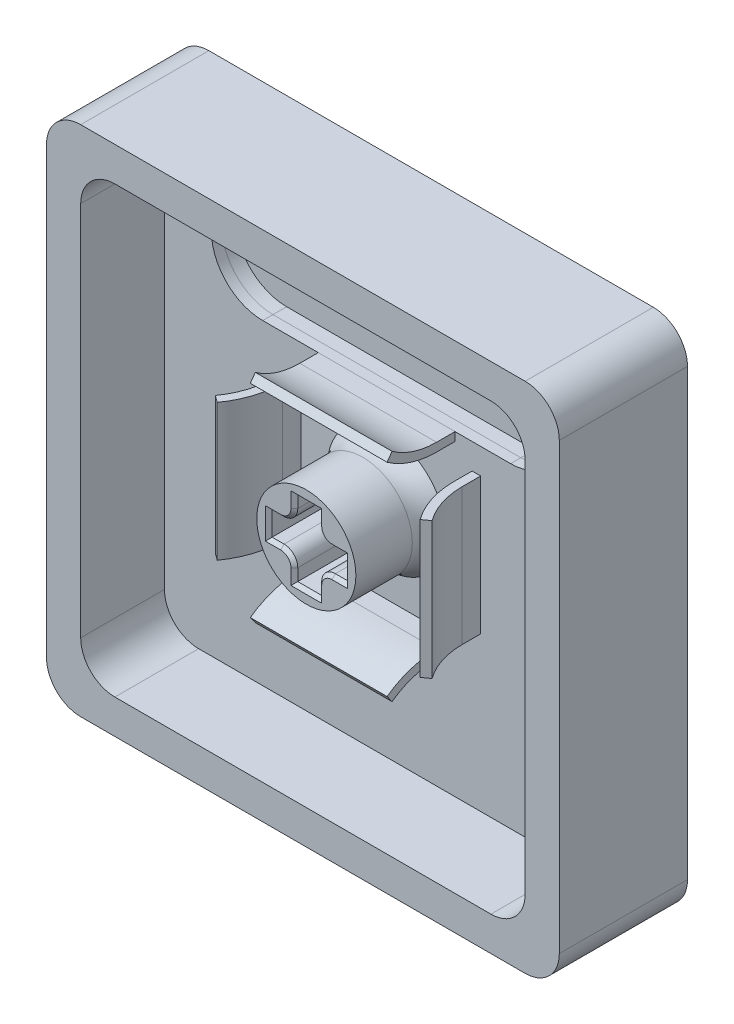
SolidWorks part; units mm, degrees
note: '?' marks a value the reader was unsure of. The reader was unsure of these and kept them because the rebuilt part matched: shared geometry of "草图1<6>", "草图1<7>".
other "标注1"
sketch "草图2" plane through (15, -15, 10) normal (0.3933, -0.7926, 0.466) x (0.9059, 0.4207, -0.0491)
ref_plane "前视基准面" through (0, 0, 0) normal (0, 0, 1) x (1, 0, 0)
ref_plane "上视基准面" through (0, 0, 0) normal (0, 1, 0) x (1, 0, 0)
ref_plane "右视基准面" through (0, 0, 0) normal (1, 0, 0) x (0, 0, -1)
sketch "草图1" plane through (0, 0, 0) normal (0, 0, 1) x (1, 0, 0)
  line L0 (-13, 15) -> (13, 15)
  line L1 (-11, 13) -> (11, 13)
  line L2 (-13, 11) -> (-13, -11)
  line L3 (-11, -13) -> (11, -13)
  line L4 (13, 11) -> (13, -11)
  line L5 (0, -13) -> (0, 13) construction
  line L6 (-13, 0) -> (13, 0) construction
  line L7 (15, 13) -> (15, -13)
  line L8 (-13, -15) -> (13, -15)
  line L9 (-15, 13) -> (-15, -13)
  line L10 (-13, -13) -> (13, -13) construction
  line L11 (-2.2, 0.7) -> (2.2, 0.7)
  line L12 (-2.2, 0.7) -> (-2.2, -0.7)
  line L13 (-2.2, -0.7) -> (2.2, -0.7)
  line L14 (2.2, 0.7) -> (2.2, -0.7)
  line L15 (0, -0.7) -> (0, 0.7) construction
  line L16 (-2.2, 0) -> (2.2, 0) construction
  line L17 (-0.7, 2.2) -> (0.7, 2.2)
  line L18 (-0.7, 2.2) -> (-0.7, -2.2)
  line L19 (-0.7, -2.2) -> (0.7, -2.2)
  line L20 (0.7, 2.2) -> (0.7, -2.2)
  line L21 (0, -2.2) -> (0, 2.2) construction
  line L22 (-0.7, 0) -> (0.7, 0) construction
  line L23 (13, 13) -> (13, -13) construction
  line L24 (-13, 13) -> (13, 13) construction
  line L25 (-13, 13) -> (-13, -13) construction
  line L26 (-15, 15) -> (-15, -15) construction
  line L27 (-15, -15) -> (15, -15) construction
  line L28 (15, 15) -> (15, -15) construction
  line L29 (-15, 15) -> (15, 15) construction
  line L36 (-13, 0) -> (-2.5, 0) construction
  circle A0 centre (0, 0) radius 2.9
  arc A1 (11, -13) -> (13, -11) centre (11, -11) ccw
  arc A2 (13, 11) -> (11, 13) centre (11, 11) ccw
  arc A3 (-13, 11) -> (-11, 13) centre (-11, 11) cw
  arc A4 (-13, -11) -> (-11, -13) centre (-11, -11) ccw
  arc A5 (-15, -13) -> (-13, -15) centre (-13, -13) ccw
  arc A6 (13, -15) -> (15, -13) centre (13, -13) ccw
  arc A7 (15, 13) -> (13, 15) centre (13, 13) ccw
  arc A8 (-15, 13) -> (-13, 15) centre (-13, 13) cw
  point P0 (0, 0)
  point P19 (13, -13)
  point P66 (0.0162, 0.0162)
  dimension "D4" = 5.8
  dimension "D9" = 2
  dimension "D1" = 30
  dimension "D2" = 30
  dimension "D5" = 4.4
  dimension "D6" = 1.4
  dimension "D7" = 4.4
  dimension "D8" = 1.4
  dimension "D3" = 2
extrude "凸台-拉伸1" add sketch "草图1" along normal blind 5.5 contours A8 L9 A5 L8 A6 L7 A7 L0 A4 L2 A3 L1 A2 L4 A1 L3
extrude "凸台-拉伸2" add sketch "草图1<6>" along normal blind 5.3 separate body contours A0 L17 L20 L11 L14 L13 L19 L18 L12
sketch "草图1<6>" plane through (0, 0, 0) normal (0, 0, 1) x (1, 0, 0) same geometry as "草图1"
extrude "凸台-拉伸3" add sketch "草图1<7>" against normal blind 2 contours L8 A6 L7 A7 L0 A8 L9 A5
sketch "草图1<7>" plane through (0, 0, 0) normal (0, 0, 1) x (1, 0, 0) same geometry as "草图1"
sketch "草图3" plane through (0, 0, 0) normal (0, 0, 1) x (1, 0, 0)
  line L8 (0.7, 0.7) -> (0.7, 2.2)
  line L10 (0.7, 0.7) -> (0.7, 2.2)
  line L15 (-0.7, 0.7) -> (-2.2, 0.7)
  line L16 (-2.2, 0.7) -> (-2.2, -0.7)
  line L17 (-2.2, -0.7) -> (-0.7, -0.7)
  line L19 (0.7, 2.2) -> (-0.7, 2.2)
  line L20 (0.7, 2.2) -> (-0.7, 2.2)
  line L21 (0.7, -0.7) -> (2.2, -0.7)
  line L22 (2.2, -0.7) -> (2.2, 0.7)
  line L23 (2.2, 0.7) -> (0.7, 0.7)
  line L27 (-0.7, 0.7) -> (-2.2, 0.7)
  line L28 (-2.2, 0.7) -> (-2.2, -0.7)
  line L29 (-2.2, -0.7) -> (-0.7, -0.7)
  line L33 (0.7, -0.7) -> (2.2, -0.7)
  line L34 (2.2, -0.7) -> (2.2, 0.7)
  line L35 (2.2, 0.7) -> (0.7, 0.7)
  line L36 (-0.7, 2.2) -> (-0.7, 0.7)
  line L37 (-0.7, 2.2) -> (-0.7, 0.7)
  line L38 (-0.7, -0.7) -> (-0.7, -2.2)
  line L39 (-0.7, -0.7) -> (-0.7, -2.2)
  line L40 (-0.7, -2.2) -> (0.7, -2.2)
  line L41 (-0.7, -2.2) -> (0.7, -2.2)
  line L42 (0.7, -2.2) -> (0.7, -0.7)
  line L43 (0.7, -2.2) -> (0.7, -0.7)
  dimension "D1" = 0
extrude "凸台-拉伸4" add sketch "草图3" along normal blind 2
sketch "草图5" plane through (0, 0, 0) normal (0, 0, 1) x (1, 0, 0)
  line L6 (7.25, 8.5) -> (-7.25, 8.5) construction
  line L7 (7.25, 5.5) -> (-7.25, 5.5)
  line L9 (7.25, 11.5) -> (-7.25, 11.5)
  line L10 (0, 0) -> (0, -50000) construction
  arc A0 (7.25, 5.5) -> (7.25, 11.5) centre (7.25, 8.5) ccw
  arc A1 (-7.25, 11.5) -> (-7.25, 5.5) centre (-7.25, 8.5) ccw
  point P2 (0, 8.5)
  dimension "D2" = 3
  dimension "D1" = 14.5
  dimension "D3" = 8.5
extrude "切除-拉伸1" cut sketch "草图5" against normal up to next
sketch "草图6" plane through (0, 0, -2) normal (0, 0, -1) x (-1, 0, 0)
  line L10 (7.25, 5.5) -> (-7.25, 5.5) construction
  line L11 (-7.25, 11.5) -> (7.25, 11.5) construction
  line L12 (7.25, 5.5) -> (-7.25, 5.5)
  line L13 (-7.25, 11.5) -> (7.25, 11.5)
  arc A0 (7.25, 5.5) -> (7.25, 11.5) centre (7.25, 8.5) ccw construction
  arc A1 (-7.25, 11.5) -> (-7.25, 5.5) centre (-7.25, 8.5) ccw construction
  arc A2 (7.25, 5.5) -> (7.25, 11.5) centre (7.25, 8.5) ccw
  arc A3 (-7.25, 11.5) -> (-7.25, 5.5) centre (-7.25, 8.5) ccw
extrude "凸台-拉伸6" add sketch "草图6" against normal blind 1.2 separate body
sketch "草图7" plane through (0, 0, 0) normal (0, 0, 1) x (1, 0, 0)
  line L0 (7.25, 5.5) -> (-7.25, 5.5) construction
  line L1 (7.25, 11.5) -> (-7.25, 11.5) construction
  line L2 (7.25, 5.5) -> (-7.25, 5.5)
  line L3 (7.25, 11.5) -> (-7.25, 11.5)
  line L4 (-13, 11) -> (-13, -11)
  line L5 (-11, -13) -> (11, -13)
  line L6 (13, -11) -> (13, 11)
  line L7 (11, 13) -> (-11, 13)
  line L8 (-13, 11) -> (-13, -11)
  line L9 (-11, -13) -> (11, -13)
  line L10 (13, -11) -> (13, 11)
  line L11 (11, 13) -> (-11, 13)
  circle A0 centre (0, 0) radius 2.9 construction
  circle A1 centre (0, 0) radius 2.9
  arc A2 (7.25, 5.5) -> (7.25, 11.5) centre (7.25, 8.5) ccw construction
  arc A3 (-7.25, 11.5) -> (-7.25, 5.5) centre (-7.25, 8.5) ccw construction
  arc A4 (-13, -11) -> (-11, -13) centre (-11, -11) ccw
  arc A5 (11, -13) -> (13, -11) centre (11, -11) ccw
  arc A6 (13, 11) -> (11, 13) centre (11, 11) ccw
  arc A7 (-11, 13) -> (-13, 11) centre (-11, 11) ccw
  arc A8 (-13, -11) -> (-11, -13) centre (-11, -11) ccw
  arc A9 (11, -13) -> (13, -11) centre (11, -11) ccw
  arc A10 (13, 11) -> (11, 13) centre (11, 11) ccw
  arc A11 (-11, 13) -> (-13, 11) centre (-11, 11) ccw
  arc A12 (7.25, 5.5) -> (7.25, 11.5) centre (7.25, 8.5) ccw
  arc A13 (-7.25, 11.5) -> (-7.25, 5.5) centre (-7.25, 8.5) ccw
  dimension "D1" = 0
ref_plane "基准面1" through (0, 0, 0) normal (0, 1, 0) x (1, 0, 0)
ref_axis "基准轴1" through (0, 0, 5.3) along (0, 0, -1)?
sketch "草图9" plane through (0, 0, 0) normal (0, 1, 0) x (1, 0, 0)
  line L0 (-15, 1.1634) -> (15, 1.1634) construction
  line L4 (15, -5.5) -> (13, -5.5)
  line L6 (15, -5.5) -> (13, -5.5) construction
  line L12 (13, -5.5) -> (-13, -5.5)
  line L14 (13, -5.5) -> (-13, -5.5) construction
  line L16 (-13, -5.5) -> (-15, -5.5)
  line L18 (-13, -5.5) -> (-15, -5.5) construction
  line L20 (5.9352, -4.5764) -> (6.3407, -4.2839)
  line L21 (5.5, 1.1634) -> (5.5, -1.6819)
  line L22 (5, 1.1634) -> (5, -1.6819)
  line L23 (0, 0) -> (0, 50000) construction
  line L24 (5.5, 1.1634) -> (5, 1.1634)
  line L29 (-15, -5.5) -> (-15, 2)
  line L30 (-15, -5.5) -> (-15, 2) construction
  line L31 (-15, 2) -> (-13, 2)
  line L32 (-15, 2) -> (-13, 2) construction
  line L33 (-13, 2) -> (13, 2)
  line L34 (-13, 2) -> (13, 2) construction
  line L35 (13, 2) -> (15, 2)
  line L36 (13, 2) -> (15, 2) construction
  line L37 (15, 2) -> (15, -5.5)
  line L38 (15, 2) -> (15, -5.5) construction
  arc A0 (5.5, -1.6819) -> (6.3407, -4.2839) centre (9.9471, -1.6819) ccw
  arc A1 (5, -1.6819) -> (5.9352, -4.5764) centre (9.9471, -1.6819) ccw
  point P1 (5.5, -1.6808)
  point P3 (6.3407, -4.2839)
  point P41 (0, 1.1634)
  dimension "D1" = 0.5
  dimension "D2" = 0.5
  dimension "D3" = 5
extrude "凸台-拉伸9" add sketch "草图9" along normal mid plane 8 separate body
ref_plane "基准面3" through (0, 0, 0) normal (-0.7071, 0.7071, 0) x (0.7071, 0.7071, 0)
sketch "草图11" plane through (0, 0, 0) normal (-0.7071, 0.7071, 0) x (0.7071, 0.7071, 0)
  line L0 (13.4246, 2) -> (20.3848, 2) construction
  line L1 (20.3848, 2) -> (20.3848, -5.5) construction
  line L2 (20.3848, -5.5) -> (17.5563, -5.5) construction
  line L3 (17.5563, -5.5) -> (16.9706, -5.5) construction
  line L4 (16.9706, -5.5) -> (1.4142, -5.5) construction
  line L5 (1.4142, -5.5) -> (-1.4142, -5.5) construction
  line L6 (-1.4142, -5.5) -> (-16.9706, -5.5) construction
  line L7 (-16.9706, -5.5) -> (-17.5563, -5.5) construction
  line L8 (-17.5563, -5.5) -> (-20.3848, -5.5) construction
  line L9 (-20.3848, -5.5) -> (-20.3848, 2) construction
  line L10 (-20.3848, 2) -> (6.364, 2) construction
  line L11 (6.364, 2) -> (12.5511, 2) construction
  line L12 (12.5511, 2) -> (13.4246, 2) construction
  line L13 (14.3563, -0.0135) -> (14.3563, -0.6104)
  line L14 (15.5563, 0) -> (15.5563, -0.6104)
  line L15 (14.3563, -0.6104) -> (15.5563, -0.6104) construction
  line L17 (14.3563, -0.0135) -> (15.5563, 0)
  line L18 (15.5563, -0.6104) -> (15.5563, -2.2135)
  line L19 (15.5563, -2.2135) -> (12.7123, -2.2135)
  line L20 (12.7123, -2.2135) -> (12.7123, -1.0135)
  line L21 (12.7123, -1.0135) -> (14.3563, -1.0135)
  line L22 (14.3563, -1.0135) -> (14.3563, -0.6104)
  dimension "D1" = 1.2
  dimension "D2" = 1.2
  dimension "D3" = 1
extrude "凸台-拉伸11" [suppressed] add sketch "草图11" along normal mid plane 2 separate body
fillet "圆角4" radius 0.8 4 edges at (-0.7, 0.7, 3.65) (0.7, 0.7, 3.65) (-0.7, -0.7, 3.65) (0.7, -0.7, 3.65)
chamfer "倒角1" distance 0.2 angle 45 16 edges at (-0.7, 1.85, 5.3) (-1.85, 0.7, 5.3) (-2.2, 0, 5.3) (-1.85, -0.7, 5.3) (-0.7, -1.85, 5.3) (0, -2.2, 5.3) (0.7, -1.85, 5.3) (1.85, -0.7, 5.3) (2.2, 0, 5.3) (1.85, 0.7, 5.3) (0.7, 1.85, 5.3) (0, 2.2, 5.3) (-0.9343, -0.9343, 5.3) (0.9343, -0.9343, 5.3) (0.9343, 0.9343, 5.3) (-0.9343, 0.9343, 5.3)
fillet "圆角5" radius 2 1 edges at (2.9, 0, 0)
sketch "草图10" plane through (0, 0, 0) normal (0, 0, 1) x (1, 0, 0)
  line L0 (7.25, 5.5) -> (-7.25, 5.5) construction
  line L1 (7.25, 11.5) -> (-7.25, 11.5) construction
  line L2 (7.25, 5.5) -> (-7.25, 5.5)
  line L3 (7.25, 11.5) -> (-7.25, 11.5)
  line L4 (-13, 11) -> (-13, -11)
  line L5 (-11, -13) -> (11, -13)
  line L6 (13, -11) -> (13, 11)
  line L7 (11, 13) -> (-11, 13)
  line L8 (-13, 11) -> (-13, -11)
  line L9 (-11, -13) -> (11, -13)
  line L10 (13, -11) -> (13, 11)
  line L11 (11, 13) -> (-11, 13)
  arc A0 (7.25, 5.5) -> (7.25, 11.5) centre (7.25, 8.5) ccw construction
  arc A1 (-7.25, 11.5) -> (-7.25, 5.5) centre (-7.25, 8.5) ccw construction
  arc A2 (7.25, 5.5) -> (7.25, 11.5) centre (7.25, 8.5) ccw
  arc A3 (-7.25, 11.5) -> (-7.25, 5.5) centre (-7.25, 8.5) ccw
  arc A4 (-13, -11) -> (-11, -13) centre (-11, -11) ccw
  arc A5 (11, -13) -> (13, -11) centre (11, -11) ccw
  arc A6 (13, 11) -> (11, 13) centre (11, 11) ccw
  arc A7 (-11, 13) -> (-13, 11) centre (-11, 11) ccw
  arc A8 (-13, -11) -> (-11, -13) centre (-11, -11) ccw
  arc A9 (11, -13) -> (13, -11) centre (11, -11) ccw
  arc A10 (13, 11) -> (11, 13) centre (11, 11) ccw
  arc A11 (-11, 13) -> (-13, 11) centre (-11, 11) ccw
  dimension "D1" = 0
extrude "凸台-拉伸10" add sketch "草图10" along normal blind 0.6 separate body
pattern_circular "阵列(圆周)6" count 4 over 360 about axis through (0, 0, 0) along (0, 0, 1) of bodies 120
